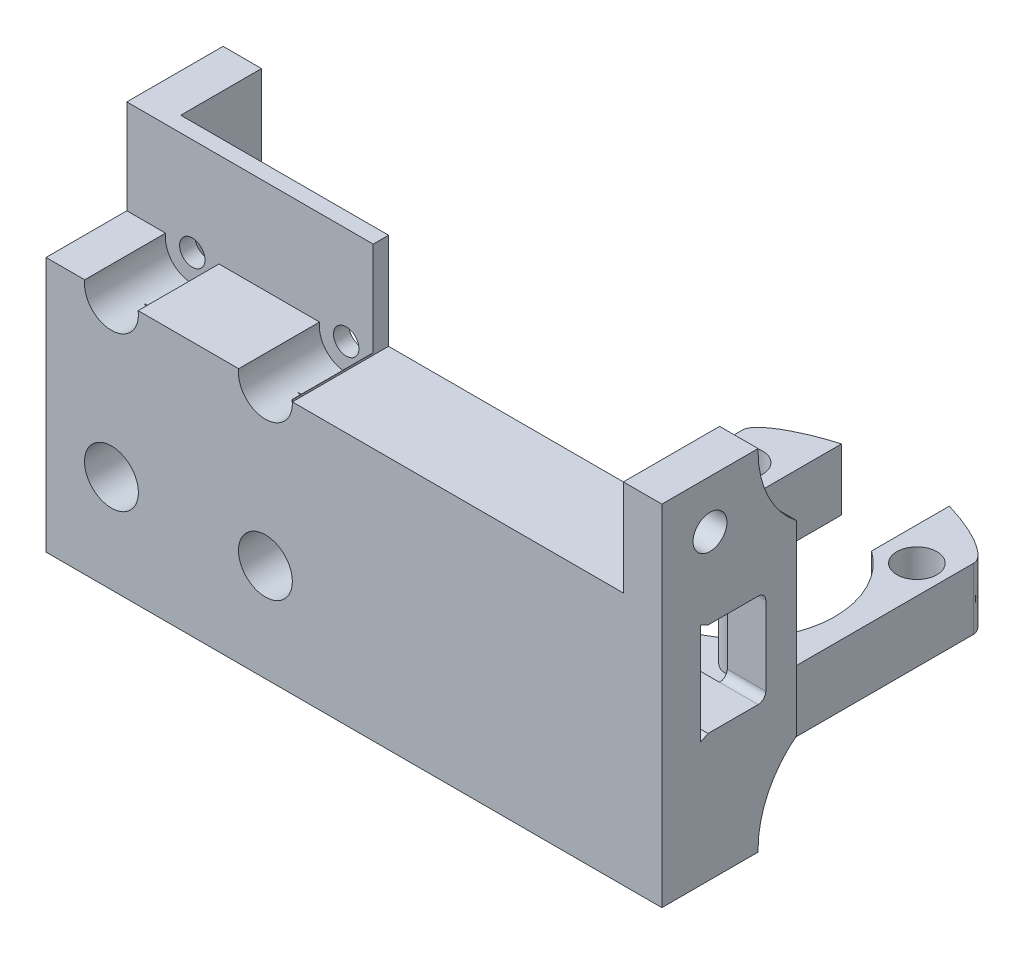
SolidWorks part; units mm, degrees
ref_plane "Front Plane" through (0, 0, 0) normal (0, 0, 1) x (1, 0, 0)
ref_plane "Top Plane" through (0, 0, 0) normal (0, 1, 0) x (1, 0, 0)
ref_plane "Right Plane" through (0, 0, 0) normal (1, 0, 0) x (0, 0, -1)
sketch "Sketch1" plane through (0, 0, 0) normal (0, 0, 1) x (1, 0, 0)
  line L1 (0, 0) -> (80, 0)
  line L2 (0, 0) -> (0, 45.4)
  line L3 (0, 45.4) -> (80, 45.4)
  line L4 (80, 0) -> (80, 45.4)
  line L5 (8.5, 32.7) -> (28.5, 32.7) construction
  line L6 (8.5, 32.7) -> (8.5, 12.7) construction
  line L7 (8.5, 12.7) -> (28.5, 12.7) construction
  line L8 (28.5, 32.7) -> (28.5, 12.7) construction
  circle A0 centre (8.5, 32.7) radius 1.65
  circle A1 centre (28.5, 32.7) radius 1.65
  circle A2 centre (28.5, 12.7) radius 1.65
  circle A3 centre (8.5, 12.7) radius 1.65
  dimension "D3" = 3.3
  dimension "D1" = 45.4
  dimension "D2" = 80
  dimension "D4" = 12.7
  dimension "D5" = 20
  dimension "D6" = 8.5
extrude "Boss-Extrude1" add sketch "Sketch1" along normal blind 12.5
sketch "Sketch2" plane through (0, 0, 0) normal (0, 0, -1) x (-1, 0, 0)
  line L0 (0, 0) -> (-80, 0) construction
  line L1 (0, 45.4) -> (-5, 45.4)
  line L2 (0, 45.4) -> (0, 0)
  line L3 (0, 0) -> (-5, 0)
  line L4 (-5, 45.4) -> (-5, 0)
  dimension "D1" = 5
extrude "Boss-Extrude2" add sketch "Sketch2" along normal blind 10.5
sketch "Sketch3" plane through (0, 0, 0) normal (0, 0, 1) x (1, 0, 0)
  line L0 (80, 0) -> (80, 45.4) construction
  line L1 (80, 28.8) -> (0, 28.8)
  line L2 (80, 28.8) -> (80, 16.6)
  line L3 (80, 16.6) -> (0, 16.6)
  line L4 (0, 28.8) -> (0, 16.6)
  line L5 (0, 0) -> (0, 45.4) construction
  line L6 (80, 22.7) -> (0, 22.7) construction
  point P10 (80, 22.7)
  dimension "D1" = 12.2
extrude "Cut-Extrude1" cut sketch "Sketch3" against normal through all and the other way blind 7.5
sketch "Sketch4" plane through (0, 0, 0) normal (0, 0, -1) x (-1, 0, 0)
  line L1 (-69.5, 0) -> (-39.5, 0)
  line L2 (-69.5, 0) -> (-69.5, 8)
  line L3 (-69.5, 8) -> (-39.5, 8)
  line L4 (-39.5, 0) -> (-39.5, 8)
  line L7 (-5, 0) -> (-80, 0) construction
  dimension "D1" = 8
  dimension "D2" = 30
  dimension "D3" = 39.5
extrude "Boss-Extrude3" add sketch "Sketch4" along normal blind 44.5
sketch "Sketch5" plane through (0, 8, 0) normal (0, 1, 0) x (1, 0, 0)
  line L0 (69.5, 44.5) -> (69.5, 0) construction
  line L1 (80, 0) -> (5, 0) construction
  circle A0 centre (54.4956, 23.5) radius 12
  dimension "D1" = 24
  dimension "D2" = 15.0044
  dimension "D3" = 23.5
extrude "Cut-Extrude2" cut sketch "Sketch5" against normal blind 45
sketch "Sketch6" plane through (0, 16.6, 0) normal (0, -1, 0) x (1, 0, 0)
  circle A3 centre (54.4956, -39.5013) radius 2.6
  circle A4 centre (65.8093, -34.815) radius 2.6
  circle A5 centre (43.1819, -34.815) radius 2.6
  dimension "D1" = 5.2
extrude "Cut-Extrude3" cut sketch "Sketch6" against normal through all both and the other way through all
fillet "Fillet1" radius 6 2 edges at (39.5, 4, -44.5) (69.5, 4, -44.5) second distance 15 conic rho 0.3 first distance on face at (39.5, 4, -22.25) first distance on face at (69.5, 4, -22.25)
sketch "Sketch8" plane through (0, 0, 12.5) normal (0, 0, 1) x (1, 0, 0)
  circle A0 centre (8.5, 32.7) radius 3.5
  circle A1 centre (28.5, 32.7) radius 3.5
  circle A2 centre (8.5, 12.7) radius 3.5
  circle A3 centre (28.5, 12.7) radius 3.5
  dimension "D1" = 7
extrude "Cut-Extrude5" cut sketch "Sketch8" against normal offset from surface (10.5 mm away) 2 up to face at (10.15, 12.7, 0)
sketch "Sketch12" plane through (0, 0, 12.5) normal (0, 0, 1) x (1, 0, 0)
  line L0 (80, 45.4) -> (0, 45.4) construction
  line L5 (0, 45.4) -> (45, 45.4)
  line L6 (0, 45.4) -> (0, 33.15)
  line L7 (0, 33.15) -> (45, 33.15)
  line L8 (45, 45.4) -> (45, 33.15)
  line L9 (0, 45.4) -> (0, 0) construction
  dimension "D1" = 12.25
  dimension "D2" = 45
extrude "Cut-Extrude8" cut sketch "Sketch12" against normal offset from surface (10.5 mm away) 2 up to face at (10.15, 32.7, 0)
sketch "Sketch13" plane through (0, 8, 0) normal (0, 1, 0) x (1, 0, 0)
  line L1 (61.4956, 51.1384) -> (47.4956, 51.1384)
  line L2 (61.4956, 51.1384) -> (61.4956, 27.8643)
  line L3 (61.4956, 27.8643) -> (47.4956, 27.8643)
  line L4 (47.4956, 51.1384) -> (47.4956, 27.8643)
  line L5 (61.4956, 51.1384) -> (47.4956, 27.8643) construction
  line L6 (61.4956, 27.8643) -> (47.4956, 51.1384) construction
  point P0 (54.4956, 39.5013)
  dimension "D1" = 14
extrude "Cut-Extrude10" cut sketch "Sketch13" against normal blind 10
sketch "Sketch14" plane through (0, 0, 0) normal (0, 0, -1) x (-1, 0, 0)
  line L1 (-80, 28.8) -> (0, 28.8)
  line L2 (-80, 28.8) -> (-80, 16.6)
  line L3 (-80, 16.6) -> (0, 16.6)
  line L4 (0, 28.8) -> (0, 16.6)
extrude "Boss-Extrude5" [suppressed] add sketch "Sketch14" against normal blind 0.5
sketch "Sketch15" plane through (0, 8, 0) normal (0, 1, 0) x (1, 0, 0)
  circle A0 centre (54.4956, 7.5013) radius 2.2
  circle A1 centre (65.8093, 12.1876) radius 2.2
  circle A2 centre (43.1819, 12.1876) radius 2.2
  dimension "D1" = 4.4
extrude "Boss-Extrude6" add sketch "Sketch15" along normal blind 8
sketch "Sketch16" plane through (0, 45.4, 0) normal (0, 1, 0) x (1, 0, 0)
  line L0 (39.5, 0) -> (69.5, 0) construction
  line L1 (75, 0) -> (32, 0)
  line L2 (75, 0) -> (75, -12.5)
  line L3 (75, -12.5) -> (32, -12.5)
  line L4 (32, 0) -> (32, -12.5)
  line L5 (80, -12.5) -> (45, -12.5) construction
  line L6 (80, -12.5) -> (80, 0) construction
  dimension "D1" = 32
  dimension "D2" = 5
extrude "Cut-Extrude11" cut sketch "Sketch16" against normal blind 12.5
sketch "Sketch17" plane through (80, 0, 0) normal (1, 0, 0) x (0, 0, -1)
  line L0 (-12.5, 45.4) -> (0, 45.4) construction
  line L1 (-6.25, 45.4) -> (-6.25, 28.8) construction
  line L2 (-7.5, 28.8) -> (0, 28.8) construction
  circle A0 centre (-6.25, 39.15) radius 2.2
  dimension "D1" = 4.4
  dimension "D2" = 6.25
extrude "Cut-Extrude12" cut sketch "Sketch17" against normal blind 10
sketch "Sketch18" plane through (80, 0, 0) normal (1, 0, 0) x (0, 0, -1)
  line L0 (-7.5, 28.8) -> (-6.5, 28.8)
  line L1 (-7.5, 28.8) -> (0, 28.8) construction
  line L2 (-6.5, 28.8) -> (-7.5, 29.3)
  line L3 (-7.5, 29.3) -> (-7.5, 28.8)
  line L4 (-7.5, 16.6) -> (-7.5, 16.1)
  line L5 (-7.5, 16.1) -> (-6.5, 16.6)
  line L6 (-7.5, 16.6) -> (0, 16.6) construction
  line L7 (-6.5, 16.6) -> (-7.5, 16.6)
  dimension "D1" = 0.5
  dimension "D2" = 1
  dimension "D3" = 1
  dimension "D4" = 0.5
extrude "Cut-Extrude13" cut sketch "Sketch18" against normal through all
sketch "Sketch19" plane through (0, 0, 0) normal (0, 0, -1) x (-1, 0, 0)
  line L0 (-80, 0) -> (-80, 16.6) construction
  line L1 (-75, 34.8) -> (-80, 34.8)
  line L2 (-75, 34.8) -> (-75, 10.6)
  line L3 (-75, 10.6) -> (-80, 10.6)
  line L4 (-80, 34.8) -> (-80, 10.6)
  line L5 (-5, 16.6) -> (-80, 16.6) construction
  line L6 (-80, 28.8) -> (-5, 28.8) construction
  line L7 (-75, 32.9) -> (-75, 45.4) construction
  dimension "D1" = 6
  dimension "D2" = 6
extrude "Boss-Extrude7" add sketch "Sketch19" along normal blind 5
sketch "Sketch20" plane through (80, 0, 0) normal (1, 0, 0) x (0, 0, -1)
  line L0 (0, 28.8) -> (0, 16.6)
  line L1 (0, 28.8) -> (1, 28.8)
  line L2 (0, 16.6) -> (1, 16.6)
  line L3 (1, 28.8) -> (1, 16.6)
  dimension "D1" = 1
extrude "Cut-Extrude14" cut sketch "Sketch20" against normal through all
sketch "Sketch21" plane through (0, 16.6, 0) normal (0, 1, 0) x (1, 0, 0)
  line L0 (5, 0) -> (5, 10.5) construction
  line L1 (0, 10.5) -> (5, 10.5)
  line L2 (0, 10.5) -> (0, 1)
  line L3 (0, 1) -> (5, 1)
  line L4 (5, 10.5) -> (5, 1)
  dimension "D1" = 9.5
extrude "Boss-Extrude8" add sketch "Sketch21" along normal up to surface (12.2 mm away) up to face at (40, 28.8, -1.25)
fillet "Fillet2" radius 1 4 edges at (77.5, 16.6, -1) (77.5, 28.8, -1) (2.5, 16.6, -1) (2.5, 28.8, -1)
fillet "Fillet3" radius 13 2 edges at (77.5, 10.6, 0) (77.5, 34.8, 0)
